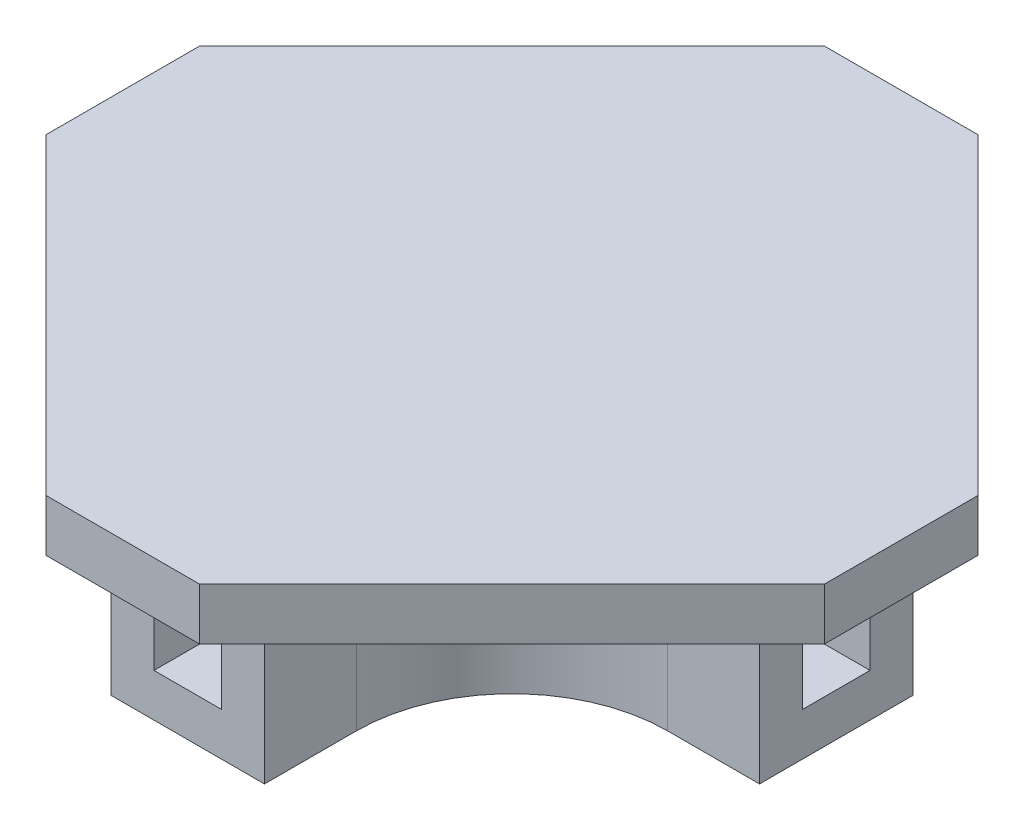
SolidWorks part; units mm, degrees
material "ABS"
ref_plane "Front Plane" through (0, 0, 0) normal (0, 0, 1) x (1, 0, 0)
ref_plane "Top Plane" through (0, 0, 0) normal (0, 1, 0) x (1, 0, 0)
ref_plane "Right Plane" through (0, 0, 0) normal (1, 0, 0) x (0, 0, -1)
sketch "Sketch1" plane through (0, 0, 0) normal (0, 1, 0) x (1, 0, 0)
  line L0 (3.7592, 11.3792) -> (3.7592, 15.875)
  line L1 (-3.7592, -15.875) -> (3.7592, -15.875)
  line L2 (-3.7592, -15.875) -> (-3.7592, -11.3792)
  line L3 (-3.7592, 15.875) -> (3.7592, 15.875)
  line L4 (3.7592, -15.875) -> (3.7592, -11.3792)
  line L5 (-3.7592, -15.875) -> (3.7592, 15.875) construction
  line L6 (-3.7592, 15.875) -> (3.7592, -15.875) construction
  line L7 (-15.875, 3.7592) -> (-11.3792, 3.7592)
  line L8 (-15.875, 3.7592) -> (-15.875, -3.7592)
  line L9 (-15.875, -3.7592) -> (-11.3792, -3.7592)
  line L10 (15.875, 3.7592) -> (15.875, -3.7592)
  line L11 (-15.875, 3.7592) -> (15.875, -3.7592) construction
  line L12 (-15.875, -3.7592) -> (15.875, 3.7592) construction
  line L13 (11.3792, 3.7592) -> (15.875, 3.7592)
  line L14 (-3.7592, 11.3792) -> (-3.7592, 15.875)
  line L15 (11.3792, -3.7592) -> (15.875, -3.7592)
  arc A0 (-3.7592, 11.3792) -> (-11.3792, 3.7592) centre (-11.3792, 11.3792) cw
  arc A1 (-11.3792, -3.7592) -> (-3.7592, -11.3792) centre (-11.3792, -11.3792) cw
  arc A2 (3.7592, -11.3792) -> (11.3792, -3.7592) centre (11.3792, -11.3792) cw
  arc A3 (11.3792, 3.7592) -> (3.7592, 11.3792) centre (11.3792, 11.3792) cw
  point P0 (0, 0)
  point P6 (0, 0)
  point P17 (-3.7592, 3.7592)
  point P22 (3.7592, -3.7592)
  point P25 (3.7592, 3.7592)
  dimension "D5" = 7.62
  dimension "D1" = 7.5184
  dimension "D2" = 7.5184
  dimension "D3" = 31.75
  dimension "D4" = 31.75
extrude "Boss-Extrude1" add sketch "Sketch1" against normal blind 7.5184
sketch "Sketch2" plane through (0, 0, 15.875) normal (0, 0, 1) x (1, 0, 0)
  line L0 (-3.7592, -7.5184) -> (-3.7592, 0) construction
  line L1 (-1.651, -5.4102) -> (1.651, -5.4102)
  line L2 (-1.651, -5.4102) -> (-1.651, -2.1082)
  line L3 (-1.651, -2.1082) -> (1.651, -2.1082)
  line L4 (1.651, -5.4102) -> (1.651, -2.1082)
  line L5 (-1.651, -5.4102) -> (1.651, -2.1082) construction
  line L6 (-1.651, -2.1082) -> (1.651, -5.4102) construction
  point P0 (0, -3.7592)
  dimension "D1" = 3.302
  dimension "D2" = 3.302
  dimension "D3" = 3.7592
  dimension "D4" = 3.7592
extrude "Cut-Extrude1" cut sketch "Sketch2" against normal blind 12.7
ref_point "Point1"
ref_axis "Axis1" through (0, -22.3909, 0) along (0, 1, 0)
pattern_circular "CirPattern1" count 4 over 360 about axis through (0, -22.3909, 0) along (0, 1, 0) of "Cut-Extrude1"
sketch "Sketch4" plane through (0, 0, 0) normal (0, 1, 0) x (1, 0, 0)
  line L0 (3.7592, 19.05) -> (19.05, 3.7592)
  line L2 (-19.05, -3.7592) -> (-19.05, 3.7592)
  line L4 (19.05, -3.7592) -> (19.05, 3.7592)
  line L7 (-3.7592, -19.05) -> (3.7592, -19.05)
  line L9 (-3.7592, 19.05) -> (3.7592, 19.05)
  line L13 (19.05, -3.7592) -> (3.7592, -19.05)
  line L14 (-3.7592, -19.05) -> (-19.05, -3.7592)
  line L15 (-19.05, 3.7592) -> (-3.7592, 19.05)
  dimension "D1" = 38.1
  dimension "D2" = 38.1
extrude "Boss-Extrude2" add sketch "Sketch4" along normal blind 2.54
